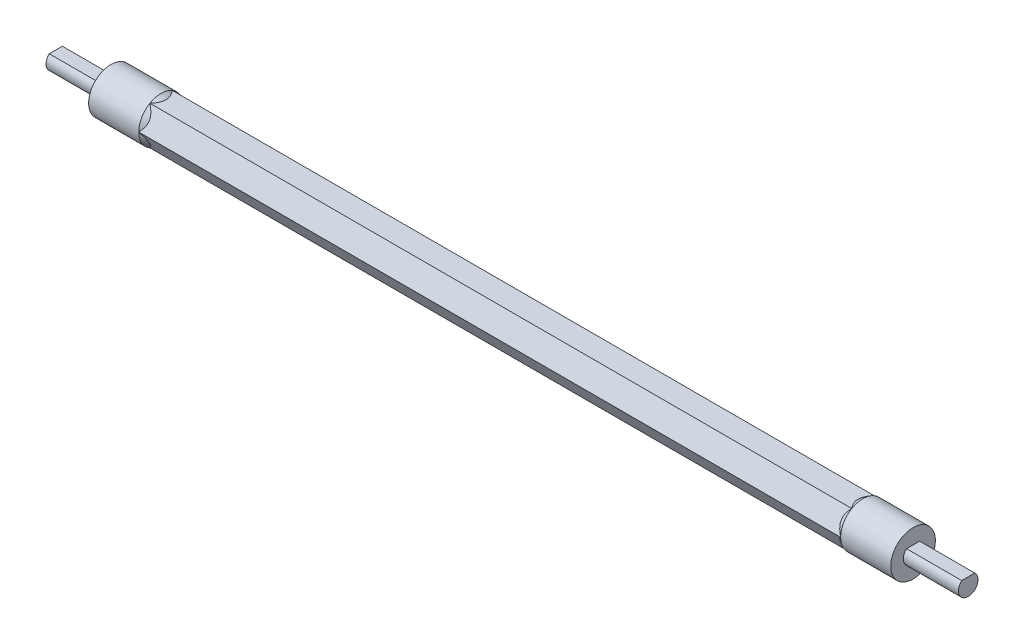
SolidWorks part; units mm, degrees
material "ABS"
ref_plane "Front Plane" through (0, 0, 0) normal (0, 0, 1) x (1, 0, 0)
ref_plane "Top Plane" through (0, 0, 0) normal (0, 1, 0) x (1, 0, 0)
ref_plane "Right Plane" through (0, 0, 0) normal (1, 0, 0) x (0, 0, -1)
sketch "Sketch1" plane through (0, 0, 0) normal (1, 0, 0) x (0, 0, -1)
  line L1 (4.45, 0) -> (2.225, 3.8538)
  line L2 (2.225, 3.8538) -> (-2.225, 3.8538)
  line L3 (-2.225, 3.8538) -> (-4.45, 0)
  line L4 (-4.45, 0) -> (-2.225, -3.8538)
  line L5 (-2.225, -3.8538) -> (2.225, -3.8538)
  line L6 (2.225, -3.8538) -> (4.45, 0)
  circle A0 centre (0, 0) radius 4.45 construction
  circle A1 centre (0, 0) radius 4.45
  dimension "D1" = 8.9
extrude "Boss-Extrude1" add sketch "Sketch1" along normal mid plane 140 contours L5 L6 L1 L2 L3 L4 region at (0, 0, 0)
extrude "Boss-Extrude2" add sketch "Sketch1<3>" along normal blind 10 from offset 70 contours L2 A1 | L1 A1 | L6 A1 | L5 A1 | L4 A1 | L3 A1 | L5 L6 L1 L2 L3 L4 region at (0, 0, 0) region at (0, -2.0469, -3.5453) region at (0, 2.0469, -3.5453) region at (0, 4.0937, 0) region at (0, -4.0937, 0) region at (0, 2.0469, 3.5453) region at (0, -2.0469, 3.5453)
sketch "Sketch1<3>" plane through (0, 0, 0) normal (1, 0, 0) x (0, 0, -1) same geometry as "Sketch1"
sketch "Sketch4" plane through (80, 0, 0) normal (1, 0, 0) x (0, 0, -1)
  line L0 (-1.3038, 1.45) -> (1.3038, 1.45)
  circle A1 centre (0, 0) radius 1.95
  circle A2 centre (0, 0) radius 4.45
  circle A3 centre (0, 0) radius 4.45
  dimension "D1" = 3.9
  dimension "D3" = 0.5
  dimension "D2" = 0
extrude "Boss-Extrude4" add sketch "Sketch4" along normal blind 11 contours L0 A1 region at (80, -0.1337, 0)
sketch "Sketch5" plane through (0, 0, 0) normal (0, 0, 1) x (1, 0, 0)
  line L0 (70, 4.45) -> (69, 3.8538)
  line L1 (70, 3.8538) -> (-70, 3.8538) construction
  line L2 (69, 3.8538) -> (69, 0)
  line L3 (70, 0) -> (-70, 0) construction
  line L4 (69, 0) -> (70, 0)
  line L5 (70, 0) -> (70, 4.45)
  dimension "D1" = 1
revolve "Revolve1" add sketch "Sketch5" angle 360 about L4
mirror "Mirror3" about plane through (0, 0, 0) normal (1, 0, 0) of "Revolve1", "Boss-Extrude2", "Boss-Extrude4"
